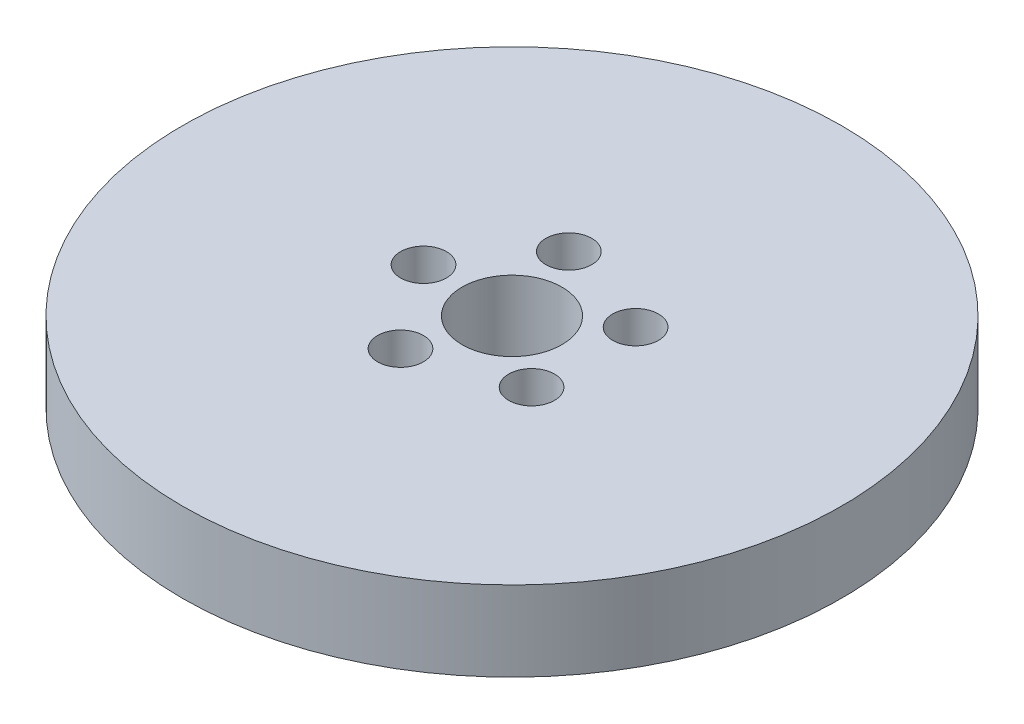
SolidWorks part; units mm, degrees
ref_plane "Front Plane" through (0, 0, 0) normal (0, 0, 1) x (1, 0, 0)
ref_plane "Top Plane" through (0, 0, 0) normal (0, 1, 0) x (1, 0, 0)
ref_plane "Right Plane" through (0, 0, 0) normal (1, 0, 0) x (0, 0, -1)
sketch "Sketch1" plane through (0, 0, 0) normal (0, 1, 0) x (1, 0, 0)
  circle A0 centre (0, 0) radius 82.5
  dimension "FLANGE_OD" = 165
extrude "Boss-Extrude1" add sketch "Sketch1" along normal blind 20
sketch "Sketch2" plane through (0, 0, 0) normal (0, 1, 0) x (1, 0, 0)
  circle A0 centre (0, 0) radius 12.5
  dimension "BORE_D" = 25
extrude "Cut-Extrude1" cut sketch "Sketch2" along normal through all
sketch "Sketch3" plane through (0, 20, 0) normal (0, 1, 0) x (1, 0, 0)
  circle A0 centre (0, 0) radius 22.1508 construction
  circle A1 centre (-22.1508, 0) radius 5.7339
  dimension "BOLT_D" = 11.4678
  dimension "BOLT_PCD" = 44.3015
extrude "Cut-Extrude2" cut sketch "Sketch3" against normal blind 15.8965
pattern_circular "CirPattern1" count 5 over 360 about axis through (0, 0, 0) along (0, 1, 0) of "Cut-Extrude2"
